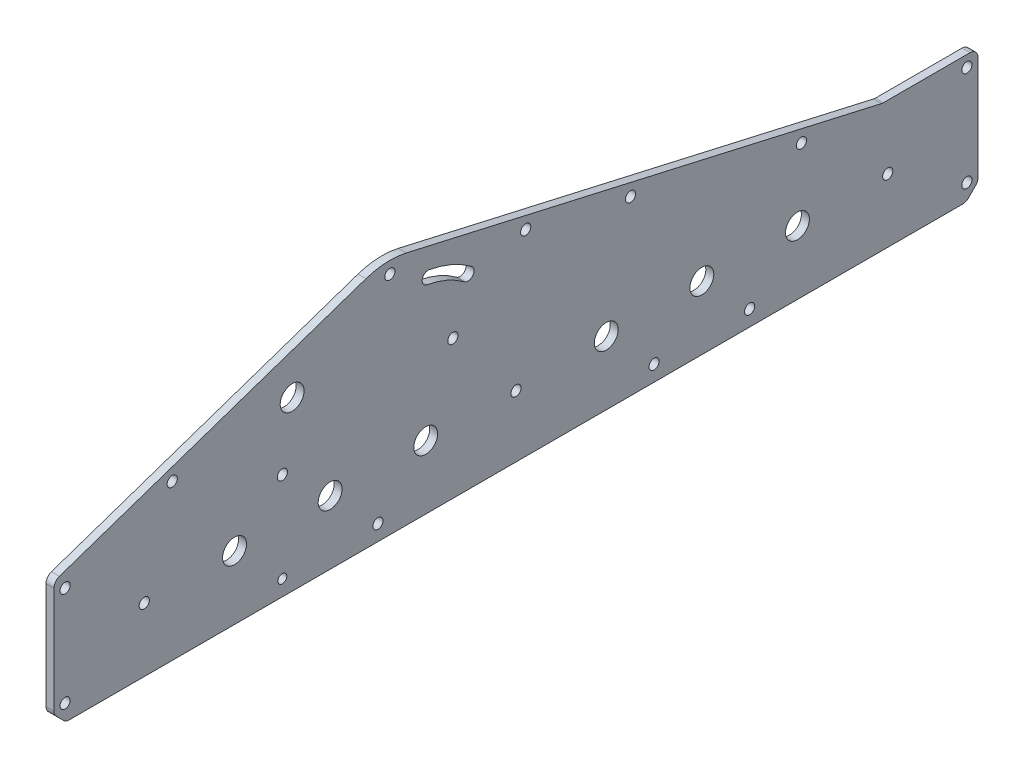
SolidWorks part; units mm, degrees
ref_plane "Front Plane" through (0, 0, 0) normal (0, 0, 1) x (1, 0, 0)
ref_plane "Top Plane" through (0, 0, 0) normal (0, 1, 0) x (1, 0, 0)
ref_plane "Right Plane" through (0, 0, 0) normal (1, 0, 0) x (0, 0, -1)
sketch "Sketch1" plane through (0, 0, 0) normal (1, 0, 0) x (0, 0, -1)
  line L0 (-184.15, 26.1937) -> (-59.8122, 68.5626)
  line L1 (-184.15, -24.6062) -> (184.15, -24.6062)
  line L2 (-184.15, -24.6062) -> (-184.15, 26.1937)
  line L3 (146.05, 26.1937) -> (184.15, 26.1937)
  line L4 (184.15, -24.6062) -> (184.15, 26.1937)
  line L9 (146.05, 26.1937) -> (-43.7083, 69.4049)
  arc A0 (-59.8122, 68.5626) -> (-43.7083, 69.4049) centre (-50.2741, 40.5715) cw
  arc A4 (-45.783, 38.8051) -> (-54.7652, 42.3379) centre (-50.2741, 40.5715) ccw construction
  arc A5 (-42.7051, 69.1579) -> (-57.8431, 69.1579) centre (-50.2741, 40.5715) ccw construction
  point P6 (0, -24.6062)
  dimension "D1" = 50.8
  dimension "D2" = 368.3
  dimension "D3" = 24.6062
  dimension "D5" = 38.1
extrude "Boss-Extrude1" add sketch "Sketch1" along normal blind 3.175
chamfer "Chamfer1" distance 4.7625 angle 45 2 edges at (1.5875, -24.6062, -184.15) (1.5875, -24.6062, 184.15)
fillet "Fillet1" radius 3.175 7 edges at (1.5875, -24.6062, -179.3875) (1.5875, -19.8437, -184.15) (1.5875, 26.1937, -184.15) (1.5875, -24.6062, 179.3875) (1.5875, -19.8437, 184.15) (1.5875, 26.1937, 184.15) (1.5875, 26.1937, -146.05)
sketch "Sketch4" plane through (3.175, 0, 0) normal (1, 0, 0) x (0, 0, -1)
  circle A0 centre (-137.0088, 37.226) radius 1.905 construction
  circle A2 centre (3.8736, 53.6853) radius 1.905 construction
  circle A3 centre (45.6663, 44.1684) radius 1.905 construction
  circle A4 centre (113.7728, 28.6594) radius 1.905 construction
  circle A5 centre (-25.1593, 30.6938) radius 2.032 construction
  circle A6 centre (-50.2741, 65.3805) radius 1.905 construction
  circle A7 centre (148.1579, 0.7938) radius 2.032 construction
  circle A8 centre (179.705, 21.7488) radius 1.905 construction
  circle A9 centre (179.705, -18.0026) radius 1.905 construction
  circle A11 centre (93.1246, -18.3223) radius 1.905 construction
  point P3 (0, 0)
  point P9 (55.0246, -18.3223)
  point P11 (-55.0246, -18.3223)
  point P13 (-179.705, 21.7487)
  point P15 (-179.705, -18.0026)
  point P17 (179.705, 21.7488)
  point P19 (148.1579, 0.7938)
  point P21 (-148.1579, 0.7937)
  point P25 (-93.1246, 17.5943)
  point P28 (-137.0088, 37.226)
  point P32 (3.8736, 53.6853)
  point P34 (45.6663, 44.1684)
  point P36 (113.7728, 28.6594)
  point P54 (-25.1593, 30.6938)
  point P59 (-50.2741, 65.3805)
  point P71 (179.705, -18.0026)
  point P76 (93.1246, -18.3223)
hole_wizard "#8 Clearance Hole1" positions "Sketch4" profile "Sketch5" hole size "#8" standard "ANSI Inch" end condition up to next
sketch "Sketch5" plane through (3.175, 0, 0) normal (0, 1, 0) x (0, 0, -1)
  line L0 (0, 0) -> (0, 3.175)
  line L1 (0, 3.175) -> (2.032, 3.175)
  line L2 (2.032, 3.175) -> (2.032, 0)
  line L5 (2.032, 0) -> (0, 0)
  line L11 (0, -6.35) -> (0, 107.95) construction
  dimension "Thru Hole Dia." = 4.064
  dimension "Thru Hole Depth" = 3.175
sketch "Sketch6" plane through (3.175, 0, 0) normal (1, 0, 0) x (0, 0, -1)
  point P0 (-93.1246, -18.3223)
hole_wizard "#8 Clearance Hole2" positions "Sketch6" profile "Sketch7" hole size "#8" standard "ANSI Inch" end condition up to next
sketch "Sketch7" plane through (3.175, -18.3223, 93.1246) normal (0, 1, 0) x (0, 0, -1)
  line L0 (0, 0) -> (0, 3.175)
  line L1 (0, 3.175) -> (1.778, 3.175)
  line L2 (1.778, 3.175) -> (1.778, 0)
  line L5 (1.778, 0) -> (0, 0)
  line L11 (0, -6.35) -> (0, 107.95) construction
  dimension "Thru Hole Dia." = 3.556
  dimension "Thru Hole Depth" = 3.175
sketch "Sketch8" plane through (3.175, 0, 0) normal (1, 0, 0) x (0, 0, -1)
  circle A0 centre (-89.211, 42.2593) radius 4.7625 construction
  circle A1 centre (35.9746, 0.7937) radius 7.239 construction
  circle A2 centre (-74.0746, 0.7938) radius 7.239 construction
  circle A3 centre (-112.1746, 0.7937) radius 4.7625 construction
  point P0 (-112.1746, 0.7937)
  point P1 (-74.0746, 0.7938)
  point P3 (-35.9746, 0.7938)
  point P5 (35.9746, 0.7937)
  point P7 (74.0746, 0.7937)
  point P9 (112.1746, 0.7937)
  point P13 (-89.211, 42.2593)
hole_wizard "3/8 Clearance Hole1" positions "Sketch8" profile "Sketch9" hole size "3/8" standard "ANSI Inch" end condition up to next
sketch "Sketch9" plane through (3.175, 0.7937, 112.1746) normal (0, 1, 0) x (0, 0, -1)
  line L0 (0, 0) -> (0, 3.175)
  line L1 (0, 3.175) -> (4.7625, 3.175)
  line L2 (4.7625, 3.175) -> (4.7625, 0)
  line L5 (4.7625, 0) -> (0, 0)
  line L11 (0, -6.35) -> (0, 107.95) construction
  dimension "Thru Hole Dia." = 9.525
  dimension "Thru Hole Depth" = 3.175
sketch "Sketch10" plane through (3.175, 0, 0) normal (1, 0, 0) x (0, 0, -1)
  arc A0 (-34.5594, 59.0407) -> (-35.4169, 54.2915) centre (-34.9881, 56.6661) ccw construction
  arc A1 (-20.5473, 47.8719) -> (-35.4169, 54.2915) centre (-41.7582, 19.1724) ccw construction
  arc A2 (-20.5473, 47.8719) -> (-17.6789, 51.753) centre (-19.1131, 49.8125) ccw construction
  arc A3 (-17.6789, 51.753) -> (-34.5594, 59.0407) centre (-41.7582, 19.1724) ccw construction
  arc A4 (-34.5594, 59.0407) -> (-35.4169, 54.2915) centre (-34.9881, 56.6661) ccw
  arc A5 (-20.5473, 47.8719) -> (-35.4169, 54.2915) centre (-41.7582, 19.1724) ccw
  arc A6 (-20.5473, 47.8719) -> (-17.6789, 51.753) centre (-19.1131, 49.8125) ccw
  arc A7 (-17.6789, 51.753) -> (-34.5594, 59.0407) centre (-41.7582, 19.1724) ccw
extrude "Cut-Extrude1" cut sketch "Sketch10" against normal through all
